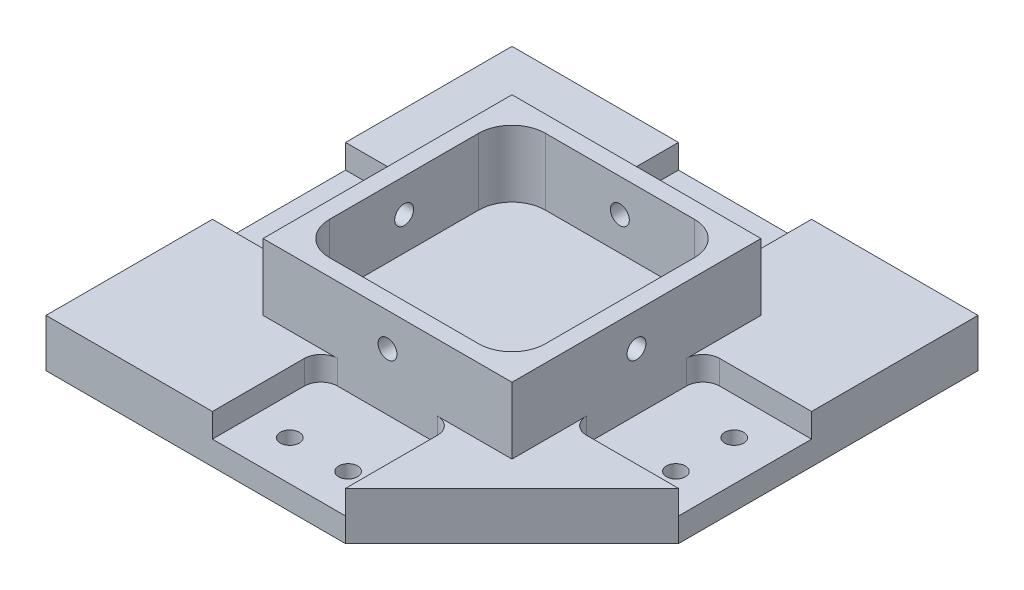
SolidWorks part; units mm, degrees
material "6061 Alloy"
ref_plane "Front Plane" through (0, 0, 0) normal (0, 0, 1) x (1, 0, 0)
ref_plane "Top Plane" through (0, 0, 0) normal (0, 1, 0) x (1, 0, 0)
ref_plane "Right Plane" through (0, 0, 0) normal (1, 0, 0) x (0, 0, -1)
sketch "Sketch1" plane through (0, 0, 0) normal (0, 1, 0) x (1, 0, 0)
  line L1 (0, 0) -> (88.9, 0)
  line L2 (0, 0) -> (0, 88.9)
  line L3 (0, 88.9) -> (88.9, 88.9)
  line L4 (88.9, 0) -> (88.9, 88.9)
  dimension "D1" = 88.9
  dimension "D2" = 88.9
extrude "Boss-Extrude1" add sketch "Sketch1" along normal blind 9.144
sketch "Sketch2" plane through (0, 9.144, 0) normal (0, 1, 0) x (1, 0, 0)
  line L0 (88.9, 88.9) -> (0, 88.9) construction
  line L1 (31.75, 88.9) -> (57.15, 88.9)
  line L2 (31.75, 88.9) -> (31.75, 67.31)
  line L3 (31.75, 67.31) -> (57.15, 67.31)
  line L4 (57.15, 88.9) -> (57.15, 67.31)
  line L5 (0, 88.9) -> (0, 0) construction
  line L6 (0, 57.15) -> (21.59, 57.15)
  line L7 (0, 57.15) -> (0, 31.75)
  line L8 (0, 31.75) -> (21.59, 31.75)
  line L9 (21.59, 57.15) -> (21.59, 31.75)
  line L10 (0, 0) -> (88.9, 0) construction
  line L11 (31.75, 0) -> (57.15, 0)
  line L12 (31.75, 0) -> (31.75, 21.59)
  line L13 (31.75, 21.59) -> (57.15, 21.59)
  line L14 (57.15, 0) -> (57.15, 21.59)
  line L15 (88.9, 0) -> (88.9, 88.9) construction
  line L16 (88.9, 57.15) -> (67.31, 57.15)
  line L17 (88.9, 57.15) -> (88.9, 31.75)
  line L18 (88.9, 31.75) -> (67.31, 31.75)
  line L19 (67.31, 57.15) -> (67.31, 31.75)
  dimension "D1" = 31.75
  dimension "D2" = 25.4
  dimension "D3" = 25.4
  dimension "D4" = 31.75
  dimension "D5" = 25.4
  dimension "D6" = 31.75
  dimension "D7" = 25.4
  dimension "D8" = 31.75
  dimension "D9" = 21.59
  dimension "D10" = 21.59
  dimension "D11" = 21.59
  dimension "D12" = 21.59
extrude "Cut-Extrude1" cut sketch "Sketch2" against normal blind 4.572
sketch "Sketch3" plane through (0, 9.144, 0) normal (0, 1, 0) x (1, 0, 0)
  line L0 (31.75, 88.9) -> (0, 88.9) construction
  line L1 (20.6375, 68.2625) -> (68.2625, 68.2625)
  line L2 (20.6375, 68.2625) -> (20.6375, 20.6375)
  line L3 (20.6375, 20.6375) -> (68.2625, 20.6375)
  line L4 (68.2625, 68.2625) -> (68.2625, 20.6375)
  line L5 (0, 31.75) -> (0, 0) construction
  line L6 (88.9, 31.75) -> (88.9, 57.15) construction
  line L7 (57.15, 88.9) -> (31.75, 88.9) construction
  line L8 (0, 57.15) -> (0, 31.75) construction
  line L9 (31.75, 0) -> (57.15, 0) construction
  circle A0 centre (28.194, 44.45) radius 2.4
  circle A1 centre (44.45, 60.706) radius 2.4
  circle A2 centre (60.706, 44.45) radius 2.4
  circle A3 centre (44.45, 28.194) radius 2.4
  dimension "D5" = 4.8
  dimension "D6" = 4.8
  dimension "D7" = 4.8
  dimension "D8" = 4.8
  dimension "D1" = 47.625
  dimension "D2" = 47.625
  dimension "D3" = 20.6375
  dimension "D4" = 20.6375
  dimension "D9" = 28.194
  dimension "D10" = 28.194
  dimension "D11" = 28.194
  dimension "D12" = 28.194
  dimension "D13" = 23.8125
  dimension "D14" = 23.8125
  dimension "D15" = 23.8125
  dimension "D16" = 23.8125
extrude "Cut-Extrude2" [suppressed] cut sketch "Sketch3" against normal through all contours A2 | A1 | A0 | A3
sketch "Sketch4" plane through (0, 4.572, 0) normal (0, 1, 0) x (1, 0, 0)
  line L0 (0, 57.15) -> (0, 31.75) construction
  line L1 (57.15, 88.9) -> (31.75, 88.9) construction
  line L2 (88.9, 31.75) -> (88.9, 57.15) construction
  line L3 (31.75, 0) -> (57.15, 0) construction
  line L4 (0, 31.75) -> (21.59, 31.75) construction
  line L5 (31.75, 21.59) -> (31.75, 0) construction
  line L6 (67.31, 31.75) -> (88.9, 31.75) construction
  line L7 (57.15, 67.31) -> (57.15, 88.9) construction
  circle A0 centre (81.28, 50.0126) radius 1.8034
  circle A1 centre (81.28, 38.8874) radius 1.8034
  circle A2 centre (50.0126, 81.28) radius 1.8034
  circle A3 centre (38.8874, 81.28) radius 1.8034
  circle A4 centre (7.62, 50.0126) radius 1.8034
  circle A5 centre (7.62, 38.8874) radius 1.8034
  circle A6 centre (38.8874, 7.62) radius 1.8034
  circle A7 centre (50.0126, 7.62) radius 1.8034
  dimension "D1" = 3.6068
  dimension "D2" = 3.6068
  dimension "D3" = 3.6068
  dimension "D4" = 3.6068
  dimension "D5" = 3.6068
  dimension "D6" = 3.6068
  dimension "D7" = 3.6068
  dimension "D8" = 3.6068
  dimension "D9" = 7.62
  dimension "D10" = 7.62
  dimension "D11" = 7.62
  dimension "D12" = 7.62
  dimension "D13" = 7.62
  dimension "D14" = 7.62
  dimension ".313" = 7.62
  dimension "D16" = 7.62
  dimension "D17" = 11.1252
  dimension "D18" = 7.1374
  dimension "D19" = 7.1374
  dimension "D20" = 11.1252
  dimension "D21" = 7.1374
  dimension "D22" = 11.1252
  dimension "D23" = 7.1374
  dimension "D24" = 11.1252
extrude "Cut-Extrude3" cut sketch "Sketch4" against normal through all
sketch "Sketch5" plane through (0, 9.144, 0) normal (0, 1, 0) x (1, 0, 0)
  line L0 (88.9, 88.9) -> (57.15, 88.9) construction
  line L1 (88.9, 31.75) -> (88.9, 57.15) construction
  circle A0 centre (44.45, 44.45) radius 6.35
  dimension "D1" = 12.7
  dimension "D2" = 44.45
  dimension "D3" = 44.45
extrude "Cut-Extrude4" [suppressed] cut sketch "Sketch5" against normal through all
sketch "Sketch6" plane through (0, 9.144, 0) normal (0, 1, 0) x (1, 0, 0)
  line L0 (88.9, 31.75) -> (57.15, 0)
  line L1 (57.15, 0) -> (88.9, 0)
  line L2 (88.9, 0) -> (88.9, 31.75)
extrude "Cut-Extrude5" cut sketch "Sketch6" against normal through all
sketch "Sketch7" plane through (0, 9.144, 0) normal (0, 1, 0) x (1, 0, 0)
  line L0 (0, 88.9) -> (0, 57.15) construction
  line L1 (20.701, 68.199) -> (68.199, 68.199)
  line L2 (20.701, 68.199) -> (20.701, 20.701)
  line L3 (20.701, 20.701) -> (68.199, 20.701)
  line L4 (68.199, 68.199) -> (68.199, 20.701)
  line L5 (0, 0) -> (31.75, 0) construction
  line L7 (23.876, 23.876) -> (65.024, 23.876)
  line L8 (23.876, 23.876) -> (23.876, 65.024)
  line L9 (23.876, 65.024) -> (65.024, 65.024)
  line L10 (65.024, 23.876) -> (65.024, 65.024)
  dimension "D1" = 47.498
  dimension "D2" = 47.498
  dimension "D3" = 20.701
  dimension "D4" = 20.701
  dimension "D5" = 3.175
  dimension "D6" = 3.175
  dimension "D7" = 3.175
  dimension "D8" = 3.175
extrude "Boss-Extrude2" add sketch "Sketch7" along normal blind 12.7 and the other way up to next (4.572 mm away)
fillet "Fillet9" radius 6.35 1 edges at (65.024, 15.494, -23.876)
fillet "Fillet10" radius 6.35 1 edges at (23.876, 15.494, -23.876)
fillet "Fillet11" radius 6.35 1 edges at (65.024, 15.494, -65.024)
fillet "Fillet12" radius 6.35 1 edges at (23.876, 15.494, -65.024)
fillet "Fillet15" radius 3.175 1 edges at (20.701, 6.858, -57.15)
fillet "Fillet16" radius 3.175 1 edges at (31.75, 6.858, -20.701)
fillet "Fillet17" radius 3.175 1 edges at (57.15, 6.858, -20.701)
fillet "Fillet18" radius 3.175 1 edges at (68.199, 6.858, -57.15)
fillet "Fillet19" radius 3.175 1 edges at (68.199, 6.858, -31.75)
fillet "Fillet20" radius 3.175 1 edges at (31.75, 6.858, -68.199)
fillet "Fillet21" radius 3.175 1 edges at (57.15, 6.858, -68.199)
fillet "Fillet22" radius 3.175 1 edges at (20.701, 6.858, -31.75)
sketch "Sketch9" plane through (0, 0, -68.199) normal (0, 0, -1) x (-1, 0, 0)
  line L0 (-68.199, 21.844) -> (-68.199, 9.144) construction
  line L1 (-68.199, 21.844) -> (-20.701, 21.844) construction
  circle A0 centre (-44.45, 15.494) radius 1.8034
  dimension "D1" = 3.6068
  dimension "D2" = 23.749
  dimension "D3" = 6.35
extrude "Cut-Extrude6" cut sketch "Sketch9" against normal through all
sketch "Sketch10" plane through (68.199, 0, 0) normal (1, 0, 0) x (0, 0, -1)
  line L0 (20.701, 21.844) -> (68.199, 21.844) construction
  line L1 (20.701, 21.844) -> (20.701, 9.144) construction
  circle A0 centre (44.45, 15.494) radius 1.8034
  dimension "D1" = 3.6068
  dimension "D2" = 6.35
  dimension "D3" = 23.749
extrude "Cut-Extrude7" cut sketch "Sketch10" against normal through all
equation "\"hinge_hole\"= 0.142in"
equation "\"D1@Sketch4\"=\"hinge_hole\""
equation "\"D2@Sketch4\"=\"hinge_hole\""
equation "\"D3@Sketch4\"=\"hinge_hole\""
equation "\"D4@Sketch4\"=\"hinge_hole\""
equation "\"D5@Sketch4\"=\"hinge_hole\""
equation "\"D6@Sketch4\"=\"hinge_hole\""
equation "\"D7@Sketch4\"=\"hinge_hole\""
equation "\"D8@Sketch4\"=\"hinge_hole\""
equation "\"hinge_hole_dist\"= 0.297 + 0.25"
equation "\".313@Sketch4\"=.3"
equation "\"hinge_hole_sep\"=0.438"
equation "\"hinge_hole_from_wall\"= ( 1 - \"hinge_hole_sep\" ) / 2"
equation "\"D17@Sketch4\"=\"hinge_hole_sep\""
equation "\"D18@Sketch4\"=\"hinge_hole_from_wall\""
equation "\"D19@Sketch4\"=\"hinge_hole_from_wall\""
equation "\"D20@Sketch4\"=\"hinge_hole_sep\""
equation "\"D21@Sketch4\"=\"hinge_hole_from_wall\""
equation "\"D22@Sketch4\"=\"hinge_hole_sep\""
equation "\"D23@Sketch4\"=\"hinge_hole_from_wall\""
equation "\"D24@Sketch4\"=\"hinge_hole_sep\""
equation "\"D9@Sketch2\"=\"hinge_hole_dist\" + (0.6-0.297)"
equation "\"D12@Sketch2\"=\"hinge_hole_dist\" + (0.6-0.297)"
equation "\"D11@Sketch2\"=\"hinge_hole_dist\" + (0.6-0.297)"
equation "\"D10@Sketch2\"=\"hinge_hole_dist\" + (0.6-0.297)"
